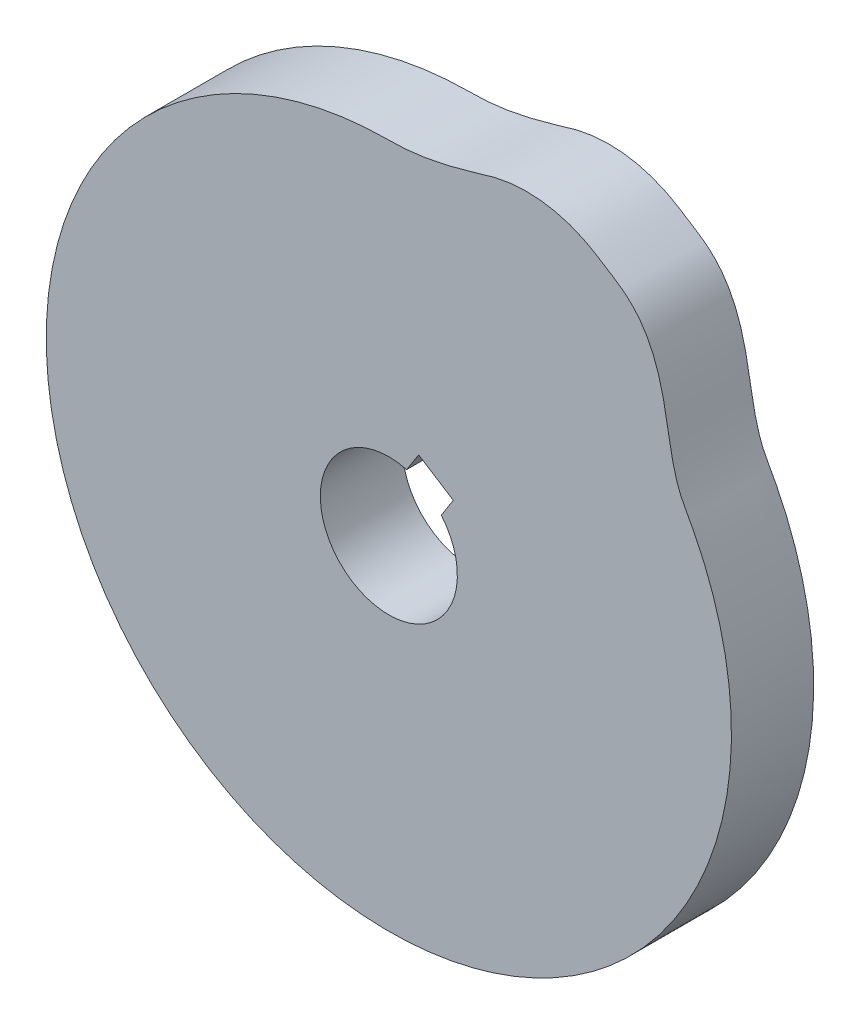
SolidWorks part; units mm, degrees
material "45"
ref_plane "前视基准面" through (0, 0, 0) normal (0, 0, 1) x (1, 0, 0)
ref_plane "上视基准面" through (0, 0, 0) normal (0, 1, 0) x (1, 0, 0)
ref_plane "右视基准面" through (0, 0, 0) normal (1, 0, 0) x (0, 0, -1)
ref_axis "基准轴1" through (0, 0, -88.99) along (0, 0, 1)
sketch "草图1" plane through (0, 0, 0) normal (0, 0, 1) x (1, 0, 0)
  arc A0 (29.5, 51.0955) -> (33.841, 48.33) centre (0, 0) cw construction
  arc A1 (43.3013, 25) -> (0, 50) centre (0, 0) cw construction
  spline S0 degree 3 poles (0, 50) (0.5829, 50) (1.4593, 50.0251) (2.629, 50.1075) (3.5139, 50.1939) (4.4059, 50.3047) (5.307, 50.4394) (6.219, 50.5977) (7.1436, 50.7791) (8.0825, 50.9831) (9.0377, 51.2091) (10.0107, 51.4566) (11.0033, 51.7245) (12.0171, 52.0129) (13.0546, 52.3181) (14.1071, 52.6477) (15.1755, 52.9563) (16.2564, 53.1982) (17.3373, 53.3826) (18.4167, 53.5069) (19.492, 53.5721) (20.5608, 53.5786) (21.6208, 53.5269) (22.6695, 53.4176) (23.7047, 53.2513) (24.7241, 53.0288) (25.7254, 52.7508) (26.7063, 52.4184) (27.9832, 51.9041) (28.9052, 51.439) (29.5, 51.0955) knots 0 0 0 0 0.057655 0.086691 0.115973 0.145583 0.175596 0.206088 0.237128 0.268787 0.301126 0.334208 0.36809 0.402825 0.438464 0.475054 0.511929 0.548418 0.584549 0.620347 0.65584 0.691054 0.726017 0.760756 0.7953 0.829674 0.863908 0.89803 0.932067 1 1 1 1 construction
  spline S1 degree 3 poles (33.841, 48.33) (34.4049, 47.9355) (35.2003, 47.2675) (36.1422, 46.2503) (36.7926, 45.4238) (37.3849, 44.5414) (37.9195, 43.6092) (38.3981, 42.6341) (38.8233, 41.6229) (39.1984, 40.583) (39.5277, 39.5218) (39.8162, 38.4466) (40.0696, 37.3646) (40.2941, 36.2827) (40.4964, 35.2073) (40.6838, 34.1445) (40.8636, 33.0995) (41.0431, 32.0769) (41.2299, 31.0807) (41.4311, 30.1138) (41.6538, 29.1785) (41.9044, 28.2762) (42.1889, 27.4073) (42.6177, 26.2999) (43.0085, 25.5064) (43.3013, 25) knots 0 0 0 0 0.080113 0.120507 0.161271 0.202479 0.244165 0.286325 0.328914 0.37185 0.41502 0.45828 0.501473 0.544424 0.586959 0.628908 0.670116 0.710452 0.749818 0.788156 0.825458 0.86177 0.897196 0.931897 1 1 1 1 construction
  spline S2 degree 3 poles (30.6076, 50.4398) (31.3413, 49.9946) (32.0651, 49.5335) (32.7786, 49.0567) (32.9104, 48.9687) (33.1731, 48.7916) (33.5651, 48.5228) (33.825, 48.3414) (33.9545, 48.2503) (34.06, 48.176) (34.2705, 48.0269) (34.5694, 47.7798) (34.7662, 47.6129) (34.8632, 47.5279) (35.0548, 47.36) (35.495, 46.9493) (36.1422, 46.2503) (36.7926, 45.4238) (37.3849, 44.5414) (37.9195, 43.6092) (38.3981, 42.6341) (38.8233, 41.6229) (39.1984, 40.583) (39.5277, 39.5218) (39.8162, 38.4466) (40.0696, 37.3646) (40.2941, 36.2827) (40.4964, 35.2073) (40.6838, 34.1445) (40.8636, 33.0995) (41.0431, 32.0769) (41.2299, 31.0807) (41.4311, 30.1138) (41.6538, 29.1785) (41.9044, 28.2762) (42.0997, 27.6797) (42.2063, 27.3825) (42.2101, 27.3718) (42.4134, 26.8067) (42.8798, 25.6981) (43.7999, 24.1381) (44.3607, 23.0758) (44.6314, 22.5397) (72.1194, -31.8898) (27.8155, -73.7866) (-24.9952, -43.304) (-77.806, -12.8214) (-63.6873, 46.4983) (-2.8067, 49.9212) (-2.205, 49.955) (-1.0004, 50.0009) (0.8094, 49.9928) (2.0133, 50.06) (2.6139, 50.1102) (2.618, 50.1105) (2.9171, 50.1356) (3.5139, 50.1939) (4.4059, 50.3047) (5.307, 50.4394) (6.219, 50.5977) (7.1436, 50.7791) (8.0825, 50.9831) (9.0377, 51.2091) (10.0107, 51.4566) (11.0033, 51.7245) (12.0171, 52.0129) (13.0546, 52.3181) (14.1071, 52.6477) (15.1755, 52.9563) (16.2564, 53.1982) (17.3373, 53.3826) (18.4167, 53.5069) (19.492, 53.5721) (20.5608, 53.5786) (21.6208, 53.5269) (22.6695, 53.4176) (23.7047, 53.2513) (24.7241, 53.0288) (25.7254, 52.7508) (26.7063, 52.4184) (27.5822, 52.0655) (28.1263, 51.8148) (28.3554, 51.7033) (28.4796, 51.6429) (28.7266, 51.5193) (29.0946, 51.328) (29.3344, 51.1909) (29.4541, 51.122) (29.5831, 51.0477) (29.8406, 50.898) (30.2251, 50.6706) (30.4803, 50.5171) (30.6076, 50.4398) (31.3413, 49.9946) (32.0651, 49.5335) knots -0.001728 0 0 0 0.009956 0.009956 0.009956 0.011795 0.013633 0.015472 0.015472 0.015472 0.016968 0.018465 0.019961 0.019961 0.019961 0.022918 0.026943 0.031006 0.035113 0.039267 0.043469 0.047714 0.051993 0.056295 0.060607 0.064911 0.069192 0.073431 0.077612 0.081719 0.085739 0.089662 0.093483 0.0972 0.100819 0.10435 0.104483 0.104483 0.104483 0.111452 0.118422 0.125391 0.125391 0.125391 0.496111 0.496111 0.496111 0.86683 0.86683 0.86683 0.873824 0.880818 0.887812 0.887812 0.887812 0.88786 0.891296 0.89477 0.898292 0.90187 0.905512 0.909226 0.913021 0.916902 0.920878 0.924953 0.929135 0.933428 0.937755 0.942036 0.946276 0.950476 0.954641 0.958772 0.962875 0.966951 0.971004 0.975037 0.979054 0.983058 0.987051 0.990008 0.990008 0.990008 0.991611 0.993213 0.994816 0.994816 0.994816 0.996544 0.998272 1 1 1 1.009956 1.009956 1.009956 weights 1 0.999841 0.999841 1 1 1 1 1 1 1 1 1 1 1 1 1 1 1 1 1 1 1 1 1 1 1 1 1 1 1 1 1 1 1 1 1 1 1 1 1 1 1 1 0.523857 0.523857 1 0.523857 0.523857 1 1 1 1 1 1 1 1 1 1 1 1 1 1 1 1 1 1 1 1 1 1 1 1 1 1 1 1 1 1 1 1 1 1 1 1 1 1 1 1 1 1 1 1 1 0.999841 0.999841 only from (30.6076, 50.4398) to (30.6076, 50.4398)
extrude "凸台-拉伸1" add sketch "草图1" along normal blind 12
sketch "草图2" plane through (0, 0, 0) normal (0, 0, 1) x (1, 0, 0)
  line L0 (2.5953, 9.6573) -> (4.3473, 12.4073)
  line L1 (4.3473, 12.4073) -> (9.4076, 9.1835)
  line L2 (9.4076, 9.1835) -> (7.6557, 6.4335)
  arc A0 (2.5953, 9.6573) -> (7.6557, 6.4335) centre (0, 0) ccw
extrude "切除-拉伸1" cut sketch "草图2" against normal blind 12 and the other way blind 12
